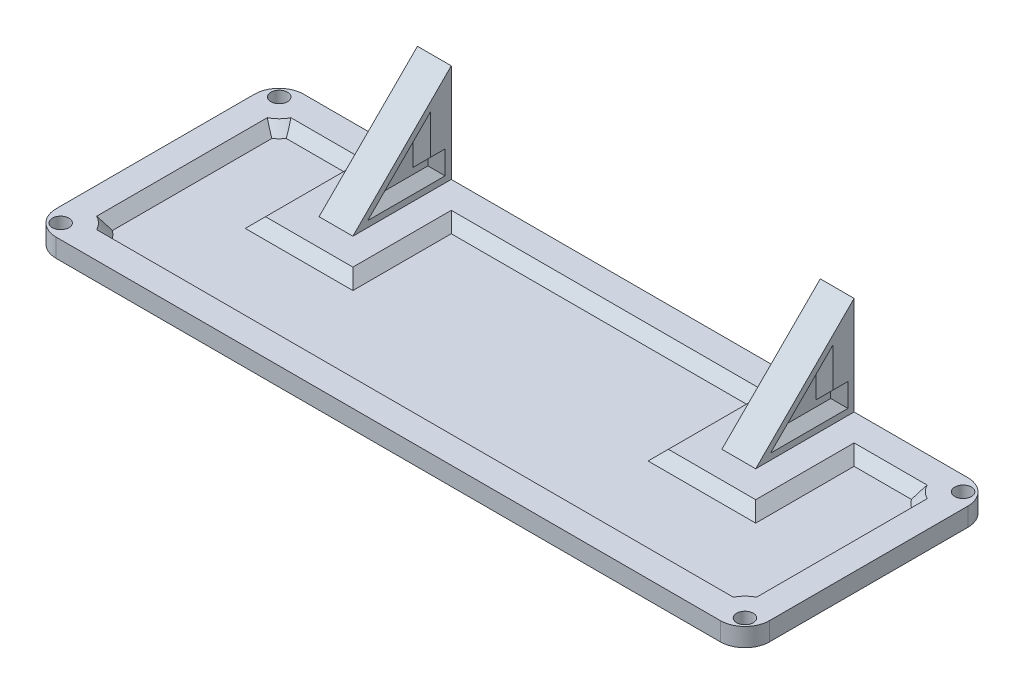
SolidWorks part; units mm, degrees
material "6061-T6 (SS)"
ref_plane "Front Plane" through (0, 0, 0) normal (0, 0, 1) x (1, 0, 0)
ref_plane "Top Plane" through (0, 0, 0) normal (0, 1, 0) x (1, 0, 0)
ref_plane "Right Plane" through (0, 0, 0) normal (1, 0, 0) x (0, 0, -1)
sketch "Sketch1" plane through (0, 0, 0) normal (0, 1, 0) x (1, 0, 0)
  line L0 (0, 0) -> (0, 20.125) construction
  line L1 (-54, -20.125) -> (54, -20.125)
  line L2 (-58, -16.125) -> (-58, 16.125)
  line L3 (-54, 20.125) -> (54, 20.125)
  line L4 (58, -16.125) -> (58, 16.125)
  line L5 (-58, -20.125) -> (58, 20.125) construction
  line L6 (-58, 20.125) -> (58, -20.125) construction
  line L7 (-0.1608, -0.0558) -> (-58, 0) construction
  arc A0 (54, 20.125) -> (58, 16.125) centre (54, 16.125) cw
  arc A1 (54, -20.125) -> (58, -16.125) centre (54, -16.125) ccw
  arc A2 (-54, -20.125) -> (-58, -16.125) centre (-54, -16.125) cw
  arc A3 (-58, 16.125) -> (-54, 20.125) centre (-54, 16.125) cw
  circle A4 centre (-55.6, 17.75) radius 1.35
  circle A5 centre (-55.6343, -17.7546) radius 1.35
  circle A6 centre (55.6343, -17.7546) radius 1.35
  circle A7 centre (55.6, 17.75) radius 1.35
  point P0 (0, 0)
  dimension "D3" = 4
  dimension "D4" = 2.7
  dimension "D1" = 116
  dimension "D2" = 40.25
  dimension "D5" = 55.6
  dimension "D6" = 17.75
extrude "Boss-Extrude1" add sketch "Sketch1" along normal blind 3
sketch "Sketch2" plane through (0, 3, 0) normal (0, 1, 0) x (1, 0, 0)
  line L8 (54, 16.125) -> (-54, 16.125)
  line L9 (-54, 16.125) -> (-54, -16.125)
  line L10 (-54, -16.125) -> (54, -16.125)
  line L11 (54, -16.125) -> (54, 16.125)
  line L12 (54, 16.125) -> (-54, 16.125)
  line L13 (-54, 16.125) -> (-54, -16.125)
  line L14 (-54, -16.125) -> (54, -16.125)
  line L15 (54, -16.125) -> (54, 16.125)
  arc A4 (-51.945, 16.125) -> (-54, 14.0839) centre (-55.6, 17.75) cw
  arc A5 (-54, -14.1037) -> (-51.9812, -16.125) centre (-55.6343, -17.7546) cw
  arc A6 (51.9812, -16.125) -> (54, -14.1037) centre (55.6343, -17.7546) cw
  arc A7 (51.945, 16.125) -> (54, 14.0839) centre (55.6, 17.75) ccw
  dimension "D2" = 4
  dimension "D1" = 4
sketch "Sketch3" plane through (0, 0, 0) normal (1, 0, 0) x (0, 0, -1)
  line L0 (20.125, 3) -> (20.125, 19)
  line L1 (20.125, 19) -> (4.125, 3)
  line L2 (-16.125, 3) -> (16.125, 3) construction
  line L3 (4.125, 3) -> (20.125, 3)
  dimension "D1" = 45
  dimension "D2" = 16
extrude "Boss-Extrude2" add sketch "Sketch3" along normal blind 5.5 from offset 30
sketch "Sketch4" plane through (0, 0, -20.125) normal (0, 0, -1) x (-1, 0, 0)
  line L0 (-35.5, 11) -> (-30, 11) construction
  line L1 (-35.5, 3) -> (-35.5, 19) construction
  line L2 (-30, 3) -> (-30, 19) construction
  circle A0 centre (-32.75, 11) radius 1.8
  dimension "D1" = 3.6
extrude "Cut-Extrude2" cut sketch "Sketch4" against normal blind 3.1 draft 8
sketch "Sketch5" plane through (35.5, 0, 0) normal (1, 0, 0) x (0, 0, -1)
  line L0 (6.5392, 4) -> (19.125, 4)
  line L1 (19.125, 4) -> (19.125, 7.8)
  line L2 (19.125, 7.8) -> (16.725, 7.8)
  line L3 (16.725, 7.8) -> (16.725, 14.1858)
  line L4 (16.725, 14.1858) -> (6.5392, 4)
  line L5 (20.125, 19) -> (4.125, 3) construction
  line L6 (4.125, 3) -> (20.125, 3) construction
  line L7 (20.125, 3) -> (20.125, 19) construction
  line L8 (20.125, 11) -> (16.725, 11) construction
  dimension "D1" = 1
  dimension "D2" = 1
  dimension "D3" = 1
  dimension "D4" = 3.4
  dimension "D5" = 3.2
ref_plane "Plane1" through (32.75, 0, 0) normal (1, 0, 0) x (0, 0, -1)
extrude "Cut-Extrude3" cut sketch "Sketch5" against normal blind 1.4
mirror "Mirror1" about plane through (32.75, 0, 0) normal (1, 0, 0) of "Cut-Extrude3"
chamfer "Chamfer2" distance 1.4 angle 45 10 edges at (31.4, 4, -12.8321) (31.4, 5.9, -19.125) (31.4, 7.8, -17.925) (31.4, 10.9929, -16.725) (31.4, 9.0929, -11.6321) (34.1, 10.9929, -16.725) (34.1, 7.8, -17.925) (34.1, 5.9, -19.125) (34.1, 4, -12.8321) (34.1, 9.0929, -11.6321)
mirror "Mirror2" about plane through (0, 0, 0) normal (1, 0, 0) of "Boss-Extrude2", "Chamfer2", "Mirror1", "Cut-Extrude3", "Cut-Extrude2"
sketch "Sketch6" plane through (0, 3, 0) normal (0, 1, 0) x (1, 0, 0)
  line L24 (-26, 0.125) -> (-39.5, 0.125)
  line L25 (-39.5, 0.125) -> (-39.5, 16.125)
  line L26 (-39.5, 16.125) -> (-54, 16.125)
  line L27 (-54, 16.125) -> (-54, -16.125)
  line L28 (-54, -16.125) -> (54, -16.125)
  line L29 (54, -16.125) -> (54, 16.125)
  line L30 (54, 16.125) -> (39.5, 16.125)
  line L31 (39.5, 16.125) -> (39.5, 0.125)
  line L32 (39.5, 0.125) -> (26, 0.125)
  line L33 (26, 0.125) -> (26, 16.125)
  line L34 (26, 16.125) -> (-26, 16.125)
  line L35 (-26, 16.125) -> (-26, 0.125)
  line L36 (-26, 0.125) -> (-39.5, 0.125)
  line L37 (-39.5, 0.125) -> (-39.5, 16.125)
  line L38 (-39.5, 16.125) -> (-54, 16.125)
  line L39 (-54, 16.125) -> (-54, -16.125)
  line L40 (-54, -16.125) -> (54, -16.125)
  line L41 (54, -16.125) -> (54, 16.125)
  line L42 (54, 16.125) -> (39.5, 16.125)
  line L43 (39.5, 16.125) -> (39.5, 0.125)
  line L44 (39.5, 0.125) -> (26, 0.125)
  line L45 (26, 0.125) -> (26, 16.125)
  line L46 (26, 16.125) -> (-26, 16.125)
  line L47 (-26, 16.125) -> (-26, 0.125)
  arc A4 (54, 14.0839) -> (51.945, 16.125) centre (55.6, 17.75) cw
  arc A5 (51.9812, -16.125) -> (54, -14.1037) centre (55.6343, -17.7546) cw
  arc A6 (-51.9812, -16.125) -> (-54.0874, -14.0658) centre (-55.6343, -17.7546) ccw
  arc A7 (-51.945, 16.125) -> (-54, 14.0839) centre (-55.6, 17.75) cw
  dimension "D1" = 4
extrude "Cut-Extrude4" cut sketch "Sketch6" against normal offset from surface (1.65 mm away) 1.35 contours L38 A7 L39 A6 L40 A5 L41 A4 L42 L43 L44 L45 L46 L47 L36 L37 region at (0, 3, 1.1551) up to face at (55.6343, 0, 19.1046)
chamfer "Chamfer3" distance 2 angle 45 16 edges at (-39.5, 1.35, -8.125) (-32.75, 1.35, -0.125) (-26, 1.35, -8.125) (0, 1.35, -16.125) (26, 1.35, -8.125) (32.75, 1.35, -0.125) (39.5, 1.35, -8.125) (45.7225, 1.35, -16.125) (52.7812, 1.35, -14.9119) (54, 1.35, 0.0099) (52.804, 1.35, 14.928) (0, 1.35, 16.125) (-52.804, 1.35, 14.928) (-54, 1.35, 0.0099) (-52.7812, 1.35, -14.9119) (-45.7225, 1.35, -16.125)
